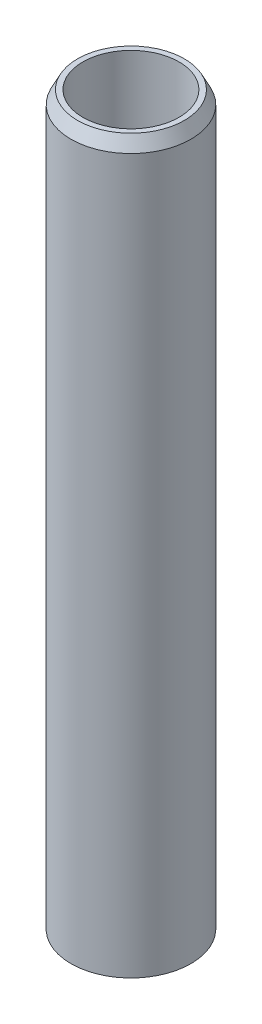
SolidWorks part; units mm, degrees
ref_plane "Front Plane" through (0, 0, 0) normal (0, 0, 1) x (1, 0, 0)
ref_plane "Top Plane" through (0, 0, 0) normal (0, 1, 0) x (1, 0, 0)
ref_plane "Right Plane" through (0, 0, 0) normal (1, 0, 0) x (0, 0, -1)
sketch "Sketch1" plane through (0, 0, 0) normal (0, 1, 0) x (1, 0, 0)
  circle A0 centre (0, 0) radius 25
  dimension "SHAFT_OD" = 50
extrude "Boss-Extrude1" add sketch "Sketch1" along normal blind 305.766
sketch "Sketch2" plane through (0, 0, 0) normal (0, 1, 0) x (1, 0, 0)
  circle A0 centre (0, 0) radius 20.0431
  dimension "BORE_D" = 40.0862
extrude "Cut-Extrude1" cut sketch "Sketch2" along normal through all
chamfer "Chamfer1" distance 5.4209 angle 26.779 2 edges at (0, 305.766, 25) (0, 0, 25) first distance on face at (0, 305.766, 25) first distance on face at (0, 0, 20.0431)
